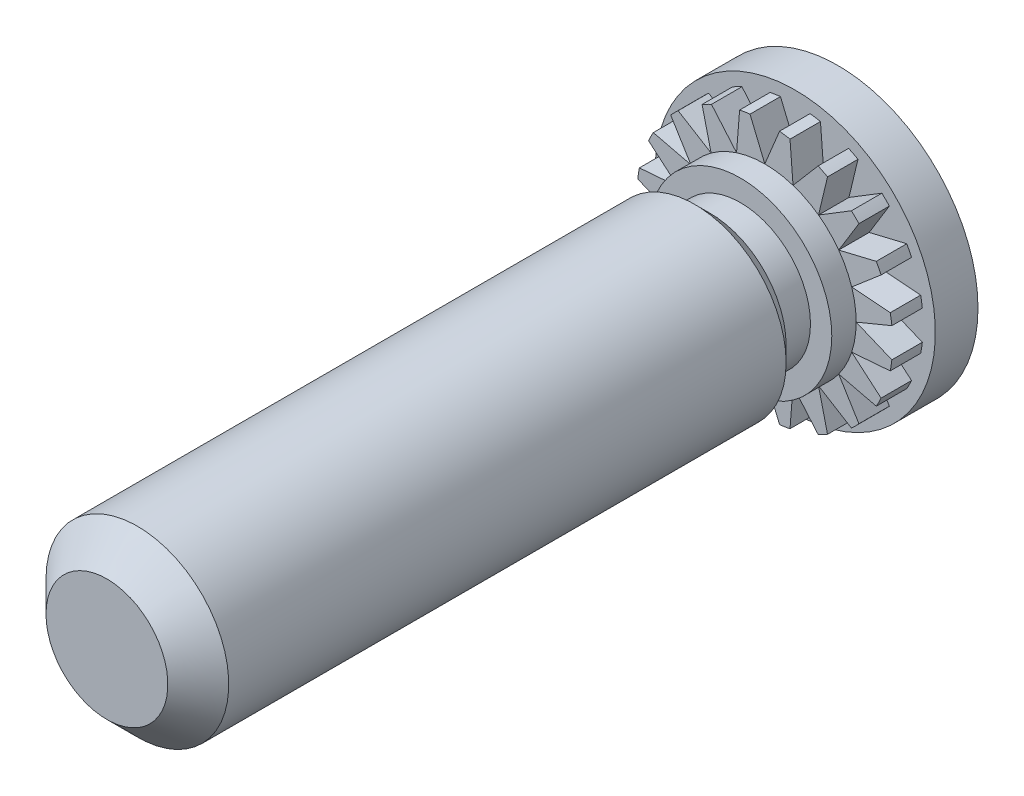
SolidWorks part; units mm, degrees
ref_plane "Спереди" through (0, 0, 0) normal (0, 0, 1) x (1, 0, 0)
ref_plane "Сверху" through (0, 0, 0) normal (0, 1, 0) x (1, 0, 0)
ref_plane "Справа" through (0, 0, 0) normal (1, 0, 0) x (0, 0, -1)
sketch "Эскиз1" plane through (0, 0, 0) normal (0, 0, 1) x (1, 0, 0)
  circle A0 centre (0, 0) radius 2.3
  dimension "D1" = 4.6
extrude "Вытянуть1" add sketch "Эскиз1" along normal blind 1.2
ref_axis "Ось1" through (0, 0, 10.6426) along (0, 0, -1)
sketch "Эскиз2" plane through (0, 0, 1.2) normal (0, 0, 1) x (1, 0, 0)
  circle A0 centre (0, 0) radius 1.5
  dimension "D1" = 3
extrude "Вытянуть2" add sketch "Эскиз2" along normal blind 1.5
sketch "Эскиз3" plane through (0, 0, 1.2) normal (0, 0, 1) x (1, 0, 0)
  line L0 (0, 0) -> (0, 2.3) construction
  line L1 (-0.3314, 2.3) -> (0.3314, 2.3)
  line L2 (0.3314, 2.3) -> (0, 1.5)
  line L3 (0, 1.5) -> (-0.3314, 2.3)
  circle A0 centre (0, 0) radius 2.3 construction
  circle A1 centre (0, 0) radius 1.5 construction
  dimension "D1" = 45
extrude "Вырез-Вытянуть1" cut sketch "Эскиз3" against normal blind 0.5
pattern_circular "Круговой массив1" count 20 over 360 about axis through (0, 0, 10.6426) along (0, 0, -1) of "Вырез-Вытянуть1"
sketch "Эскиз4" plane through (0, 0, 0) normal (0, 1, 0) x (1, 0, 0)
  line L0 (0, -1.85) -> (1.5, -1.85) construction
  line L1 (0, -4.6295) -> (0, 2.1879) construction
  line L2 (-1.5, -2.7) -> (1.5, -2.7) construction
  line L3 (1.5, -1.6) -> (1.15, -1.6)
  line L4 (1.5, -1.6) -> (1.5, -2.1)
  line L5 (1.5, -2.1) -> (1.15, -2.1)
  line L6 (1.15, -1.6) -> (1.15, -2.1)
  dimension "D1" = 0.5
  dimension "D2" = 0.6
  dimension "D3" = 1.5
  dimension "D4" = 0.35
revolve "Вырез-Повернуть1" cut sketch "Эскиз4" angle 360 about axis through (0, 0, 10.6426) along (0, 0, -1)
sketch "Эскиз6" plane through (0, 0, 0) normal (1, 0, 0) x (0, 0, -1)
  line L0 (-2.7, 0) -> (-12, 0)
  line L1 (-2.7, 1.5) -> (-2.7, -1.5) construction
  line L2 (-10.6426, 0) -> (0.6656, 0) construction
  line L3 (-12, 0) -> (-12, -1.5)
  line L4 (-12, -1.5) -> (-2.7, -1.5)
  line L5 (-2.7, -1.5) -> (-2.7, 0)
  line L6 (0, -2.3) -> (0, 2.3) construction
  dimension "D1" = 12
  dimension "D2" = 1.5
revolve "Повернуть1" add sketch "Эскиз6" angle 360 about L0
chamfer "Фаска2" distance 0.5 angle 45 1 edges at (-1.5, 0, 12)
sketch "Эскиз7" plane through (0, 0, 1.2) normal (0, 0, 1) x (1, 0, 0)
  circle A0 centre (0, 0) radius 2.1
  circle A1 centre (0, 0) radius 2.3
  arc A2 (-1.0781, 2.0317) -> (-1.5991, 1.6532) centre (0, 0) ccw construction
  dimension "D1" = 0.2
extrude "Вырез-Вытянуть2" cut sketch "Эскиз7" against normal up to surface (0.5 mm away) up to face at (-1.9266, 0.626, 0.7)
chamfer "Фаска3" distance 0.25 angle 45 1 edges at (1.5, 0, 2.1)
